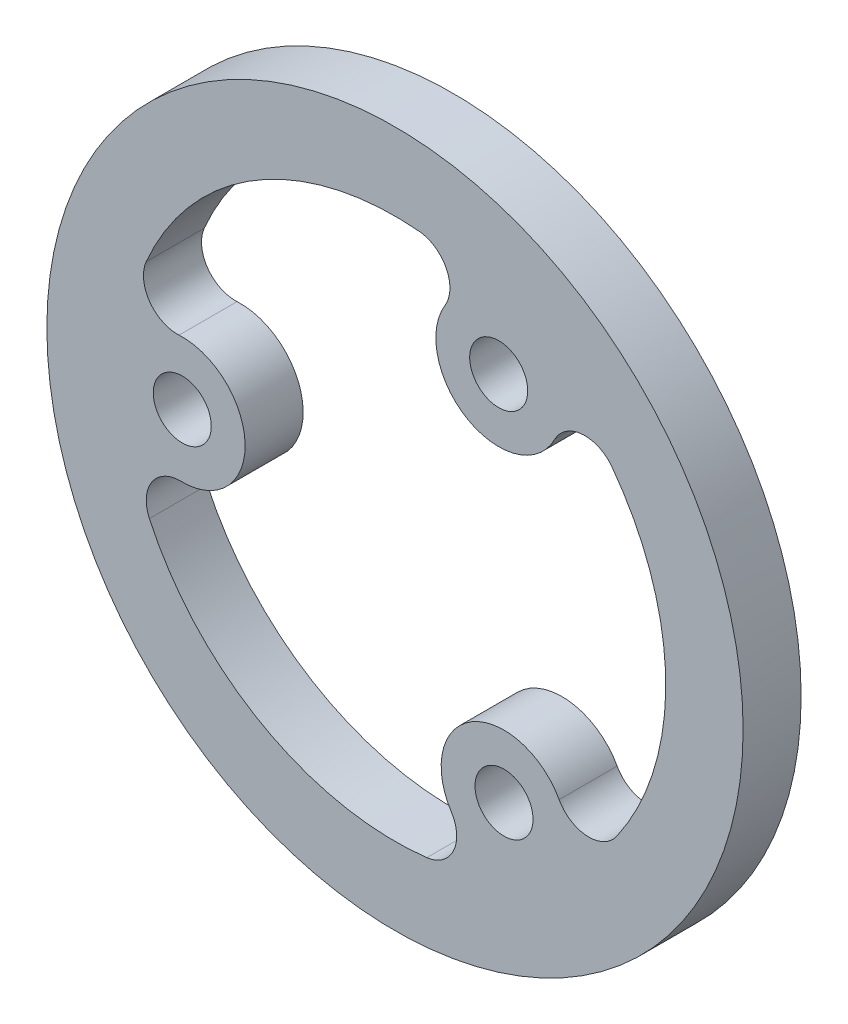
SolidWorks part; units mm, degrees
ref_plane "Plan de face" through (0, 0, 0) normal (0, 0, 1) x (1, 0, 0)
ref_plane "Plan de dessus" through (0, 0, 0) normal (0, 1, 0) x (1, 0, 0)
ref_plane "Plan de droite" through (0, 0, 0) normal (1, 0, 0) x (0, 0, -1)
sketch "Esquisse1" plane through (0, 0, 0) normal (0, 0, 1) x (1, 0, 0)
  line L0 (5.3623, 9.6045) -> (0, 0) construction
  line L1 (-10.9989, -0.1583) -> (5.3623, 9.6045) construction
  line L2 (5.3623, 9.6045) -> (5.6365, -9.4461) construction
  line L3 (5.6365, -9.4461) -> (-10.9989, -0.1583) construction
  circle A0 centre (0, 0) radius 18
  circle A3 centre (-10.9989, -0.1583) radius 1.5
  arc A8 (-11.0721, -3.4075) -> (-11.1656, 3.0874) centre (-10.9989, -0.1583) ccw
  circle A9 centre (5.3623, 9.6045) radius 1.5
  arc A13 (8.487, -7.885) -> (2.909, -11.2134) centre (5.6365, -9.4461) ccw
  circle A14 centre (5.6365, -9.4461) radius 1.5
  circle A19 centre (0, 0) radius 7.75 construction
  circle A21 centre (0, 0) radius 9 construction
  arc A22 (11.4536, -8.0507) -> (11.2172, 8.3771) centre (0, 0) ccw
  arc A23 (8.487, -7.885) -> (11.4536, -8.0507) centre (10.0219, -7.0444) ccw
  arc A24 (1.6462, -13.9029) -> (2.909, -11.2134) centre (1.4404, -12.165) ccw
  arc A26 (-11.0721, -3.4075) -> (-12.699, -5.8938) centre (-11.1116, -5.157) ccw
  arc A27 (-12.8633, 5.5258) -> (-11.1656, 3.0874) centre (-11.2554, 4.8351) ccw
  arc A28 (2.5851, 11.2925) -> (8.2566, 8.126) centre (5.3623, 9.6045) ccw
  arc A29 (2.5851, 11.2925) -> (1.2453, 13.9445) centre (1.0897, 12.2014) ccw
  arc A30 (11.2172, 8.3771) -> (8.2566, 8.126) centre (9.815, 7.3299) ccw
  arc A31 (1.2453, 13.9445) -> (-12.8633, 5.5258) centre (0, 0) ccw
  arc A32 (-12.699, -5.8938) -> (1.6462, -13.9029) centre (0, 0) ccw
  point P32 (0, 0)
  point P37 (0, 0)
  dimension "D1" = 36
  dimension "D2" = 3
  dimension "D3" = 3
  dimension "D4" = 3
  dimension "D5" = 15.5
  dimension "D7" = 18
  dimension "D9" = 3.5
  dimension "D10" = 3.5
  dimension "D14" = 28
  dimension "D6" = 11
  dimension "D8" = 19.0506
extrude "Boss.-Extru.1" add sketch "Esquisse1" along normal blind 3
